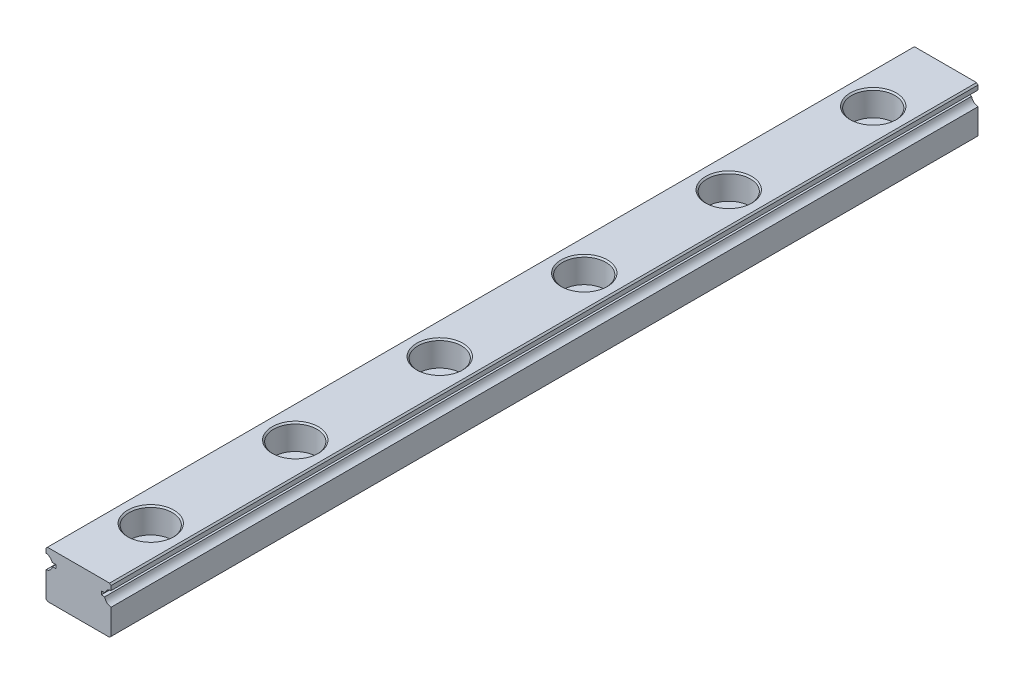
SolidWorks part; units mm, degrees
ref_plane "Спереди" through (0, 0, 0) normal (0, 0, 1) x (1, 0, 0)
ref_plane "Сверху" through (0, 0, 0) normal (0, 1, 0) x (1, 0, 0)
ref_plane "Справа" through (0, 0, 0) normal (1, 0, 0) x (0, 0, -1)
sketch "Sketch1" plane through (0, 0, 0) normal (0, 0, 1) x (1, 0, 0)
  line L0 (0, 0) -> (0, 4.3706) construction
  line L1 (-4.3, -3.25) -> (4.3, -3.25)
  line L2 (-4.5, -3.05) -> (-4.5, 0.455)
  line L3 (-4.3, 3.25) -> (4.3, 3.25)
  line L4 (4.5, -3.05) -> (4.5, 0.455)
  line L5 (-4.5, -3.25) -> (4.5, 3.25) construction
  line L6 (-4.5, 3.25) -> (4.5, -3.25) construction
  line L7 (-4.5, 2.445) -> (-4.5, 3.05)
  line L8 (4.5, 2.445) -> (4.5, 3.05)
  line L9 (-4.5, -3.05) -> (-4.3, -3.25)
  line L10 (4.3, -3.25) -> (4.5, -3.05)
  line L11 (4.3, 3.25) -> (4.5, 3.05)
  line L12 (-4.5, 3.05) -> (-4.3, 3.25)
  line L13 (3.6177, 1.2625) -> (3.1501, 1.2625)
  line L14 (-3.6177, 1.2625) -> (-3.1501, 1.2625)
  line L15 (3.1501, 1.2625) -> (3.1501, 1.7625)
  line L16 (-3.6501, 1.7625) -> (-3.1501, 1.7625)
  line L17 (-3.1501, 1.2625) -> (-3.1501, 1.7625)
  line L18 (3.6501, 1.7625) -> (3.1501, 1.7625)
  arc A0 (-4.5, 2.445) -> (-3.6501, 1.7625) centre (-4.6, 1.45) cw
  arc A1 (4.5, 2.445) -> (3.6501, 1.7625) centre (4.6, 1.45) ccw
  arc A2 (-3.6177, 1.2625) -> (-4.5, 0.455) centre (-4.6, 1.45) cw
  arc A3 (3.6177, 1.2625) -> (4.5, 0.455) centre (4.6, 1.45) ccw
  point P0 (0, 0)
  dimension "D4" = 1
  dimension "D5" = 0.1
  dimension "D1" = 9
  dimension "D2" = 6.5
  dimension "D3" = 1.8
  dimension "D6" = 0.5
  dimension "D7" = 0.5
extrude "Extrude1" add sketch "Sketch1" along normal blind 120
sketch "Sketch2" plane through (0, 3.25, 0) normal (0, 1, 0) x (1, 0, 0)
  line L0 (0, 0) -> (0, -10) construction
  circle A0 centre (0, -10) radius 1.75
  circle A1 centre (0, -10) radius 3
  dimension "D1" = 3.5
  dimension "D2" = 6
  dimension "D3" = 10
extrude "Extrude2" cut sketch "Sketch2" against normal up to next contours A0 region at (0, 3.25, 10)
extrude "Extrude4" cut sketch "Sketch" against normal blind 3.5
sketch "Sketch" plane through (0, 3.25, 0) normal (0, 1, 0) x (1, 0, 0) same geometry as "Sketch2"
chamfer "Chamfer1" distance 0.2 angle 45 2 edges at (0, -3.25, 11.75) (0, 3.25, 13)
pattern_linear "LPattern1" count 6 spacing 20 along (0, 0, 1) of "Extrude4", "Chamfer1", "Extrude2"
